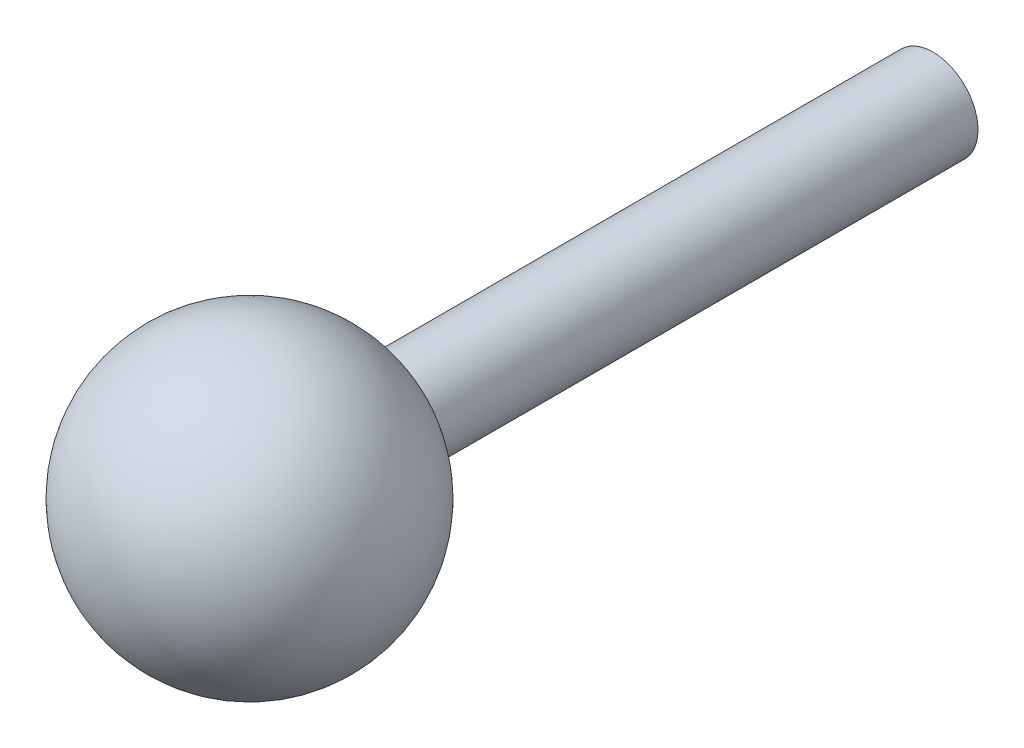
SolidWorks part; units mm, degrees
ref_plane "Front Plane" through (0, 0, 0) normal (0, 0, 1) x (1, 0, 0)
ref_plane "Top Plane" through (0, 0, 0) normal (0, 1, 0) x (1, 0, 0)
ref_plane "Right Plane" through (0, 0, 0) normal (1, 0, 0) x (0, 0, -1)
sketch "Sketch1" plane through (0, 0, 0) normal (0, 0, 1) x (1, 0, 0)
  circle A0 centre (0, 0) radius 1.25
  dimension "D1" = 2.5
extrude "Boss-Extrude1" add sketch "Sketch1" along normal blind 19
sketch "Sketch2" plane through (0, 0, 19) normal (0, 0, 1) x (1, 0, 0)
  line L0 (0, -4) -> (0, 4)
  arc A0 (0, 4) -> (0, -4) centre (0, 0) ccw
  point P4 (0, 0)
  dimension "D1" = 8
revolve "Revolve1" add sketch "Sketch2" angle 360 about L0 region at (-1.824, 0, 19)
